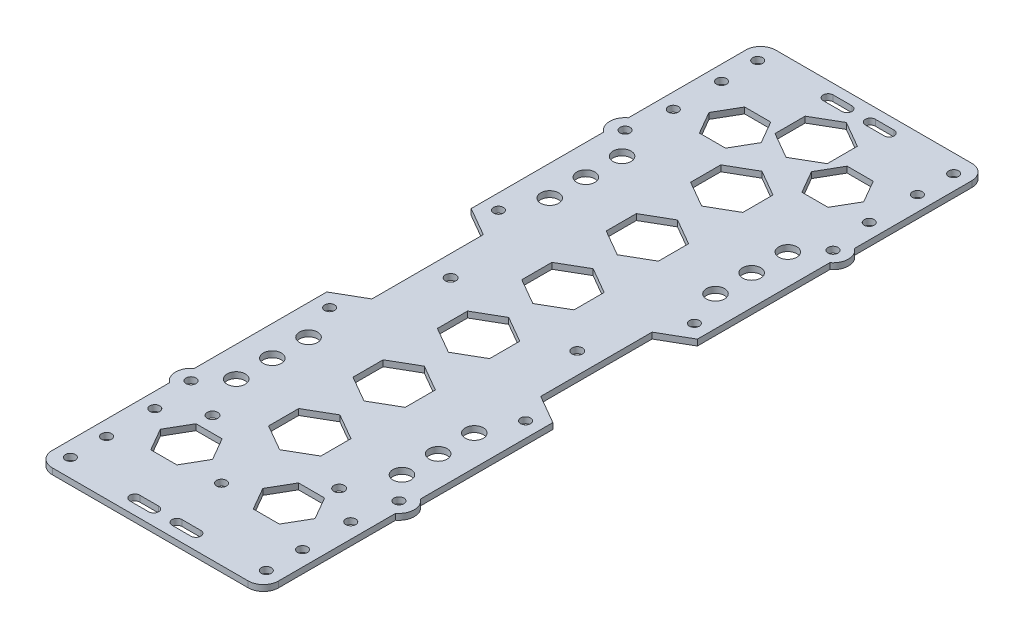
SolidWorks part; units mm, degrees
ref_plane "Front Plane" through (0, 0, 0) normal (0, 0, 1) x (1, 0, 0)
ref_plane "Top Plane" through (0, 0, 0) normal (0, 1, 0) x (1, 0, 0)
ref_plane "Right Plane" through (0, 0, 0) normal (1, 0, 0) x (0, 0, -1)
sketch "Sketch1" plane through (0, 0, 0) normal (0, 1, 0) x (1, 0, 0)
  line L0 (37.5251, 115) -> (37.5251, 23.9745)
  line L1 (-37.5, 115.5) -> (-37.5, 23.96)
  line L2 (-200, -200) -> (200, -200) construction
  line L7 (-200, -200) -> (-200, 200) construction
  line L8 (-200, 200) -> (200, 200) construction
  line L11 (200, -200) -> (200, 200) construction
  line L14 (-200, -200) -> (200, 200) construction
  line L17 (0, 0) -> (60, 0) construction
  line L23 (0, 120) -> (0, -120) construction
  line L24 (0, 0) -> (-60, 0) construction
  line L52 (-32.5251, 120) -> (32.5251, 120)
  line L63 (-32.5, -120) -> (32.5, -120)
  line L69 (28, 18.4752) -> (37.5251, 23.9745)
  line L70 (-37.5, -23.96) -> (-28, -18.4752)
  line L71 (-28, -18.4752) -> (-28, 18.4752)
  line L73 (37.5251, -23.9745) -> (37.5251, -115)
  line L74 (-28, 18.4752) -> (-37.5, 23.96)
  line L78 (28, -18.4752) -> (28, 18.4752)
  line L79 (37.5251, -23.9745) -> (28, -18.4752)
  line L80 (-37.5, -23.96) -> (-37.5, -114.5)
  line L81 (-60, 36.9504) -> (-67.2154, 32.7846) [skipped]
  line L82 (-92, 0) -> (-92, -18.4752) [skipped]
  line L83 (-76, -27.7128) -> (-60, -36.9504) [skipped]
  line L84 (-200, 200) -> (200, -200) construction
  circle A7 centre (200, 200) radius 177.8 construction
  circle A8 centre (-200, 200) radius 177.8 construction
  circle A9 centre (-200, -200) radius 177.8 construction
  circle A10 centre (200, -200) radius 177.8 construction
  circle A29 centre (-27.4977, 64) radius 3
  circle A30 centre (-27.4989, 52) radius 3
  circle A31 centre (-27.5, 40) radius 3
  arc A54 (32.5251, 120) -> (37.5251, 115) centre (32.5251, 115) cw
  arc A67 (-37.5, 115.5) -> (-32.5251, 120) centre (-32.5251, 115) cw
  arc A68 (32.5, -120) -> (37.5251, -115) centre (32.5251, -115.0001) ccw
  arc A69 (-37.5, -114.5) -> (-32.5, -120) centre (-32.5251, -115.0001) ccw
  circle A70 centre (27.5, 40) radius 3
  circle A71 centre (27.4989, 52) radius 3
  circle A72 centre (27.4977, 64) radius 3
  circle A73 centre (27.4977, -64) radius 3
  circle A74 centre (27.4989, -52) radius 3
  circle A75 centre (27.5, -40) radius 3
  circle A76 centre (-27.5, -40) radius 3
  circle A77 centre (-27.4989, -52) radius 3
  circle A78 centre (-27.4977, -64) radius 3
  circle A79 centre (-34.4977, 72) radius 1.65
  circle A80 centre (34.4977, 72) radius 1.65
  circle A81 centre (34.4977, -72) radius 1.65
  circle A82 centre (-34.4977, -72) radius 1.65
  point P22 (0, 0)
  point P26 (-200, 200)
  point P36 (-37.5, 119.5)
  point P54 (0, 0)
  dimension "D4" = 60
  dimension "D5" = 400
  dimension "D7" = 5
  dimension "D8" = 10
  dimension "D9" = 355.6
  dimension "D10" = 8
  dimension "D11" = 40
  dimension "D13" = 3.3
  dimension "D23" = 6
  dimension "D27" = 12
  dimension "D28" = 12
  dimension "D6" = 60
  dimension "D12" = 7
  dimension "D1" = 240
  dimension "D3" = 400
extrude "Boss-Extrude1" add sketch "Sketch1" along normal blind 2
sketch "Sketch2" plane through (0, 2, 0) normal (0, 1, 0) x (1, 0, 0)
  line L21 (0, 120) -> (0, -120) construction
  line L28 (32.5251, 120) -> (-32.5251, 120) construction
  line L31 (-32.5, -120) -> (32.5, -120) construction
  line L33 (28, -18.4752) -> (28, 18.4752) construction
  line L36 (28, 0) -> (-28, 0) construction
  line L49 (-28, 18.4752) -> (-28, -18.4752) construction
  circle A11 centre (-34.4977, 72) radius 5.0909
  circle A12 centre (34.4977, 72) radius 5.0909
  circle A13 centre (34.4977, -72) radius 5.0909
  circle A14 centre (-34.4977, -72) radius 5.0909
  circle A15 centre (-34.4977, 72) radius 1.65
  circle A16 centre (34.4977, 72) radius 1.65
  circle A17 centre (34.4977, -72) radius 1.65
  circle A18 centre (-34.4977, -72) radius 1.65
extrude "Boss-Extrude2" add sketch "Sketch2" against normal up to surface (2 mm away) up to face at (-27.4989, 0, -49)
sketch "Sketch3" plane through (0, 2, 0) normal (0, 1, 0) x (1, 0, 0)
  line L0 (0, 120) -> (0, -120) construction
  line L1 (32.5251, 120) -> (-32.5251, 120) construction
  line L2 (-32.5, -120) -> (32.5, -120) construction
  line L3 (-10.1252, 115) -> (-3.8748, 115) construction
  line L4 (-28, 0) -> (28, 0) construction
  line L5 (-28, 18.4752) -> (-28, -18.4752) construction
  line L6 (28, -18.4752) -> (28, 18.4752) construction
  line L7 (-35.9641, 114) -> (-34.2321, 111) construction
  line L8 (-34.2321, 111) -> (-30.7679, 111) construction
  line L9 (-30.7679, 111) -> (-29.0359, 114) construction
  line L10 (-29.0359, 114) -> (-30.7679, 117) construction
  line L11 (-30.7679, 117) -> (-34.2321, 117) construction
  line L12 (-34.2321, 117) -> (-35.9641, 114) construction
  line L31 (0, 82.9095) -> (-8.6603, 77.9095)
  line L32 (0, 110.9095) -> (-8.6603, 105.9095)
  line L33 (-8.6603, 105.9095) -> (-8.6603, 95.9095)
  line L34 (-8.6603, 95.9095) -> (0, 90.9095)
  line L35 (0, 90.9095) -> (8.6603, 95.9095)
  line L36 (8.6603, 95.9095) -> (8.6603, 105.9095)
  line L37 (8.6603, 105.9095) -> (0, 110.9095)
  line L38 (-8.6603, 77.9095) -> (-8.6603, 67.9095)
  line L39 (-8.6603, 67.9095) -> (0, 62.9095)
  line L40 (0, 62.9095) -> (8.6603, 67.9095)
  line L41 (8.6603, 67.9095) -> (8.6603, 77.9095)
  line L42 (8.6603, 77.9095) -> (0, 82.9095)
  line L43 (0, 54.9095) -> (-8.6603, 49.9095)
  line L44 (-8.6603, 49.9095) -> (-8.6603, 39.9095)
  line L45 (-8.6603, 39.9095) -> (0, 34.9095)
  line L46 (0, 34.9095) -> (8.6603, 39.9095)
  line L47 (8.6603, 39.9095) -> (8.6603, 49.9095)
  line L48 (8.6603, 49.9095) -> (0, 54.9095)
  line L49 (0, 26.9095) -> (-8.6603, 21.9095)
  line L50 (-8.6603, 21.9095) -> (-8.6603, 11.9095)
  line L51 (-8.6603, 11.9095) -> (0, 6.9095)
  line L52 (0, 6.9095) -> (8.6603, 11.9095)
  line L53 (8.6603, 11.9095) -> (8.6603, 21.9095)
  line L54 (8.6603, 21.9095) -> (0, 26.9095)
  line L55 (0, -1.0905) -> (-8.6603, -6.0905)
  line L56 (-8.6603, -6.0905) -> (-8.6603, -16.0905)
  line L57 (-8.6603, -16.0905) -> (0, -21.0905)
  line L58 (0, -21.0905) -> (8.6603, -16.0905)
  line L59 (8.6603, -16.0905) -> (8.6603, -6.0905)
  line L60 (8.6603, -6.0905) -> (0, -1.0905)
  line L61 (0, -29.0905) -> (-8.6603, -34.0905)
  line L62 (-8.6603, -34.0905) -> (-8.6603, -44.0905)
  line L63 (-8.6603, -44.0905) -> (0, -49.0905)
  line L64 (0, -49.0905) -> (8.6603, -44.0905)
  line L65 (8.6603, -44.0905) -> (8.6603, -34.0905)
  line L66 (8.6603, -34.0905) -> (0, -29.0905)
  line L67 (0, -57.0905) -> (-8.6603, -62.0905)
  line L68 (-8.6603, -62.0905) -> (-8.6603, -72.0905)
  line L69 (-8.6603, -72.0905) -> (0, -77.0905)
  line L70 (0, -77.0905) -> (8.6603, -72.0905)
  line L71 (8.6603, -72.0905) -> (8.6603, -62.0905)
  line L72 (8.6603, -62.0905) -> (0, -57.0905)
  line L119 (-17, 120) -> (-17, 91) construction
  line L121 (-10.1252, 116.65) -> (-3.8748, 116.65)
  line L122 (-10.1252, 113.35) -> (-3.8748, 113.35)
  line L123 (10.1252, 115) -> (3.8748, 115) construction
  line L124 (10.1252, 116.65) -> (3.8748, 116.65)
  line L125 (10.1252, 113.35) -> (3.8748, 113.35)
  line L126 (10.1252, -115) -> (3.8748, -115) construction
  line L127 (10.1252, -116.65) -> (3.8748, -116.65)
  line L128 (10.1252, -113.35) -> (3.8748, -113.35)
  line L129 (-10.1252, -115) -> (-3.8748, -115) construction
  line L130 (-10.1252, -116.65) -> (-3.8748, -116.65)
  line L131 (-10.1252, -113.35) -> (-3.8748, -113.35)
  line L132 (0, 90.9095) -> (0, 82.9095) construction
  line L134 (12.6699, 83.5) -> (8.3397, 91)
  line L135 (-8.3397, 91) -> (-12.6699, 98.5)
  line L137 (-12.6699, 98.5) -> (-21.3301, 98.5)
  line L138 (-21.3301, 98.5) -> (-25.6603, 91)
  line L139 (-25.6603, 91) -> (-21.3301, 83.5)
  line L140 (-21.3301, 83.5) -> (-12.6699, 83.5)
  line L141 (-12.6699, 83.5) -> (-8.3397, 91)
  line L142 (21.3301, 83.5) -> (12.6699, 83.5)
  line L143 (25.6603, 91) -> (21.3301, 83.5)
  line L144 (21.3301, 98.5) -> (25.6603, 91)
  line L145 (12.6699, 98.5) -> (21.3301, 98.5)
  line L146 (8.3397, 91) -> (12.6699, 98.5)
  line L147 (21.3301, -83.5) -> (12.6699, -83.5)
  line L148 (25.6603, -91) -> (21.3301, -83.5)
  line L149 (21.3301, -98.5) -> (25.6603, -91)
  line L150 (12.6699, -98.5) -> (21.3301, -98.5)
  line L151 (8.3397, -91) -> (12.6699, -98.5)
  line L152 (12.6699, -83.5) -> (8.3397, -91)
  line L153 (-12.6699, -83.5) -> (-8.3397, -91)
  line L154 (-21.3301, -83.5) -> (-12.6699, -83.5)
  line L155 (-25.6603, -91) -> (-21.3301, -83.5)
  line L156 (-21.3301, -98.5) -> (-25.6603, -91)
  line L157 (-12.6699, -98.5) -> (-21.3301, -98.5)
  line L158 (-8.3397, -91) -> (-12.6699, -98.5)
  line L159 (-34.2321, -117) -> (-35.9641, -114) construction
  line L160 (-30.7679, -117) -> (-34.2321, -117) construction
  line L161 (-29.0359, -114) -> (-30.7679, -117) construction
  line L162 (-30.7679, -111) -> (-29.0359, -114) construction
  line L163 (-34.2321, -111) -> (-30.7679, -111) construction
  line L164 (-35.9641, -114) -> (-34.2321, -111) construction
  circle A0 centre (-32.5, 114) radius 1.65
  circle A1 centre (-32.5, 102) radius 1.65
  circle A2 centre (-32.5, 86) radius 1.65
  circle A3 centre (-32.5, 28) radius 1.65
  circle A4 centre (-7, 115) radius 1.65 construction
  circle A5 centre (-32.5, 114) radius 3 construction
  circle A6 centre (0, 100.9095) radius 8.6603 construction
  circle A7 centre (7, 115) radius 1.65 construction
  circle A8 centre (32.5, 28) radius 1.65
  circle A9 centre (32.5, 86) radius 1.65
  circle A10 centre (32.5, 102) radius 1.65
  circle A11 centre (32.5, 114) radius 1.65
  circle A12 centre (0, 72.9095) radius 8.6603 construction
  circle A13 centre (0, 44.9095) radius 8.6603 construction
  circle A18 centre (7, -115) radius 1.5 construction
  circle A19 centre (-7, -115) radius 1.5 construction
  circle A24 centre (0, 16.9095) radius 8.6603 construction
  circle A25 centre (0, -11.0905) radius 8.6603 construction
  circle A26 centre (0, -39.0905) radius 8.6603 construction
  circle A27 centre (0, -67.0905) radius 8.6603 construction
  circle A28 centre (-17, 91) radius 7.5 construction
  circle A30 centre (32.5, -114) radius 1.65
  circle A31 centre (32.5, -102) radius 1.65
  circle A38 centre (32.5, -86) radius 1.65
  circle A39 centre (32.5, -28) radius 1.65
  circle A40 centre (0, -96.35) radius 1.65
  arc A41 (-10.1252, 116.65) -> (-10.1252, 113.35) centre (-10.1252, 115) ccw
  arc A42 (-3.8748, 113.35) -> (-3.8748, 116.65) centre (-3.8748, 115) ccw
  arc A43 (10.1252, 116.65) -> (10.1252, 113.35) centre (10.1252, 115) cw
  arc A44 (3.8748, 113.35) -> (3.8748, 116.65) centre (3.8748, 115) cw
  arc A45 (10.1252, -116.65) -> (10.1252, -113.35) centre (10.1252, -115) ccw
  arc A46 (3.8748, -113.35) -> (3.8748, -116.65) centre (3.8748, -115) ccw
  arc A47 (-10.1252, -116.65) -> (-10.1252, -113.35) centre (-10.1252, -115) cw
  arc A48 (-3.8748, -113.35) -> (-3.8748, -116.65) centre (-3.8748, -115) cw
  circle A49 centre (-32.5, -114) radius 3 construction
  circle A50 centre (-32.5, -28) radius 1.65
  circle A51 centre (-32.5, -86) radius 1.65
  circle A52 centre (-32.5, -102) radius 1.65
  circle A53 centre (-32.5, -114) radius 1.65
  point P7 (0, -96.35)
  point P166 (-7, 115)
  point P173 (7, 115)
  point P186 (7, -115)
  point P193 (-7, -115)
  dimension "D1" = 3.3
  dimension "D3" = 7
  dimension "D4" = 6
  dimension "D5" = 7
  dimension "D6" = 7
  dimension "D7" = 17
  dimension "D8" = 12
  dimension "D9" = 58
  dimension "D10" = 16
  dimension "D17" = 5
  dimension "D19" = 3.3
  dimension "D20" = 1.65
  dimension "D15" = 29
  dimension "D2" = 6
  dimension "D11" = 20
  dimension "D12" = 9.0905
  dimension "D13" = 7
extrude "Cut-Extrude1" cut sketch "Sketch3" against normal blind 10
sketch "Sketch4" plane through (0, 2, 0) normal (0, 1, 0) x (1, 0, 0)
  line L0 (0, -120) -> (0, 120) construction
  line L1 (-32.5, -120) -> (32.5, -120) construction
  line L2 (32.5251, 120) -> (-32.5251, 120) construction
  line L7 (-21, -78.35) -> (-21, 0.65) construction
  line L8 (-21, 0.65) -> (21, 0.65) construction
  line L9 (21, 0.65) -> (21, -78.35) construction
  line L10 (21, -78.35) -> (-21, -78.35) construction
  circle A0 centre (-21, -78.35) radius 1.75
  circle A1 centre (21, -78.35) radius 1.75
  circle A4 centre (-21, 0.65) radius 1.75
  circle A5 centre (21, 0.65) radius 1.75
  circle A6 centre (0, -96.35) radius 1.65 construction
  dimension "D1" = 21
  dimension "D2" = 3.5
  dimension "D3" = 18
  dimension "D4" = 21
  dimension "D5" = 18
  dimension "D6" = 79
extrude "Cut-Extrude2" cut sketch "Sketch4" against normal blind 10
